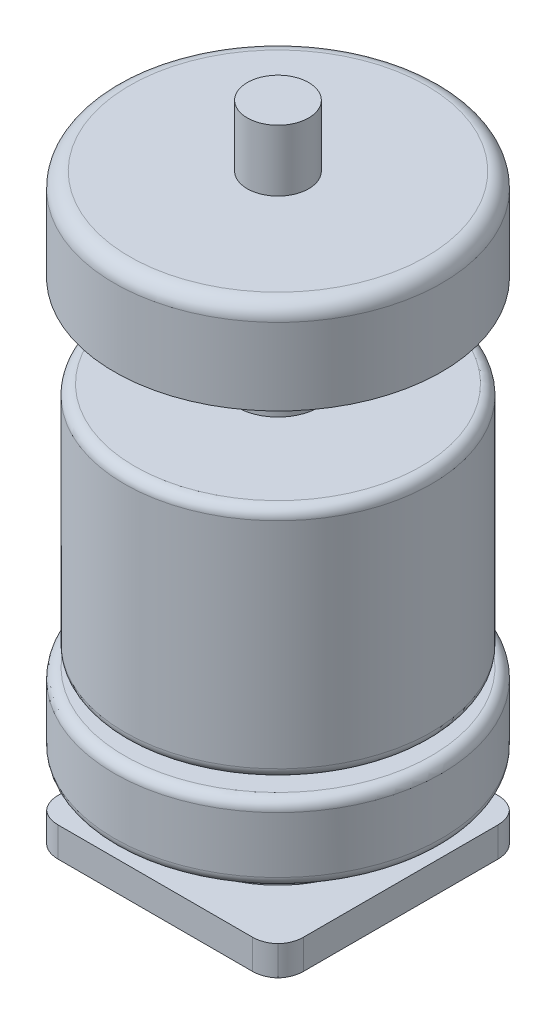
SolidWorks part; units mm, degrees
ref_plane "Ebene vorne" through (0, 0, 0) normal (0, 0, 1) x (1, 0, 0)
ref_plane "Ebene oben" through (0, 0, 0) normal (0, 1, 0) x (1, 0, 0)
ref_plane "Ebene rechts" through (0, 0, 0) normal (1, 0, 0) x (0, 0, -1)
ref_plane "Ebene1" through (0, 0, 10) normal (0, 0, 1) x (1, 0, 0)
ref_plane "Ebene2" through (0, 0, 0) normal (0, 1, 0) x (1, 0, 0)
ref_plane "Ebene3" through (0, 0, 0) normal (1, 0, 0) x (0, 0, -1)
sketch "Skizze1" plane through (0, 0, 0) normal (1, 0, 0) x (0, 0, -1)
  line L0 (-10, 34.65) -> (-10, -34.65) construction
  line L1 (-26, 31.3494) -> (6, 31.3494)
  line L2 (-26, 31.3494) -> (-26, -31.6506)
  line L3 (-26, -31.6506) -> (6, -31.6506)
  line L4 (6, 31.3494) -> (6, -31.6506)
  line L5 (-10, 31.3494) -> (-10, -31.6506)
  point P4 (-10, 31.3494)
  dimension "D1" = 63
  dimension "D2" = 32
revolve "Rotation1" add sketch "Skizze1" angle 360 about L5 region at (0, -0.1506, 18)
sketch "Skizze2" plane through (0, 31.3494, 0) normal (0, 1, 0) x (1, 0, 0)
  circle A0 centre (0, -10) radius 3
  circle A1 centre (0, -10) radius 16
  point P4 (0, 0)
ref_axis "Achse1" through (0, 55, 10) along (0, -1, 0)
sketch "Skizze6" plane through (0, 0, 10) normal (0, 0, 1) x (1, 0, 0)
  line L0 (0, 55) -> (0, -55) construction
  line L1 (-3, 31.3494) -> (-17.0561, 31.3494)
  line L2 (-3, 31.3494) -> (-3, 25.3494)
  line L3 (-3, 25.3494) -> (-17.0561, 25.3494)
  line L4 (-17.0561, 31.3494) -> (-17.0561, 25.3494)
  line L6 (3, 31.3494) -> (-3, 31.3494) construction
  point P8 (0, 0)
  dimension "D1" = 3
  dimension "D2" = 6
revolve "Schnitt-Rotation1" cut sketch "Skizze6" angle 360 about axis through (0, 55, 10) along (0, -1, 0)
sketch "Skizze7" plane through (0, -31.6506, 0) normal (0, -1, 0) x (1, 0, 0)
  line L0 (17.6, 10) -> (-17.6, 10) construction
  line L1 (12, 22) -> (-12, 22)
  line L2 (12, 22) -> (12, -2)
  line L3 (12, -2) -> (-12, -2)
  line L4 (-12, 22) -> (-12, -2)
  line L5 (0, -55) -> (0, 55) construction
  circle A1 centre (0, 10) radius 16.9706
  point P6 (-12, 10)
  point P7 (0, 22)
  point P10 (0, -2)
  point P13 (0, 0)
  circle M5 centre (0, 10) radius 16
  dimension "D1" = 24
  dimension "D2" = 24
extrude "Schnitt-Linear austragen2" cut sketch "Skizze7" against normal blind 2.9 contours L1 M5 | L2 M5 | L3 M5 | L4 M5 region at (0, -31.6506, 23.6185) region at (13.6185, -31.6506, 10) region at (-13.6185, -31.6506, 10) region at (0, -31.6506, -3.6185)
sketch "Skizze8" plane through (0, 0, 10) normal (0, 0, 1) x (1, 0, 0)
  line L1 (-9, -28.7506) -> (-18.6979, -28.7506)
  line L2 (-9, -28.7506) -> (-9, -24.1451)
  line L3 (-9, -24.1451) -> (-18.6979, -24.1451)
  line L4 (-18.6979, -28.7506) -> (-18.6979, -24.1451)
  line L5 (10.583, -31.6506) -> (-10.583, -31.6506) construction
  line L6 (0, 55) -> (0, -55) construction
  dimension "D1" = 2.9
  dimension "D2" = 9
revolve "Schnitt-Rotation2" cut sketch "Skizze8" angle 360 about axis through (0, 55, 10) along (0, -1, 0)
fillet "Verrundung1" radius 2.7 8 edges at (-12, -30.2006, -0.583) (-10.583, -30.2006, -2) (-10.583, -30.2006, 22) (-12, -30.2006, 20.583) (10.583, -30.2006, 22) (12, -30.2006, 20.583) (10.583, -30.2006, -2) (12, -30.2006, -0.583)
sketch "Skizze9" plane through (0, 0, 10) normal (0, 0, 1) x (1, 0, 0)
  line L0 (16, 25.3494) -> (-16, 25.3494) construction
  line L1 (4, 7.3494) -> (17.5123, 7.3494)
  line L2 (4, 7.3494) -> (4, 16.3494)
  line L3 (4, 16.3494) -> (17.5123, 16.3494)
  line L4 (17.5123, 7.3494) -> (17.5123, 16.3494)
  line L5 (0, 55) -> (0, -55) construction
  dimension "D1" = 9
  dimension "D2" = 9
  dimension "D3" = 4
revolve "Schnitt-Rotation3" cut sketch "Skizze9" angle 360 about axis through (0, 55, 10) along (0, -1, 0)
sketch "Skizze11" plane through (0, 0, 10) normal (0, 0, 1) x (1, 0, 0)
  line L0 (9.5079, -31.6506) -> (-9.5079, -31.6506) construction
  line L1 (-15, -16.6506) -> (-17.7938, -16.6506)
  line L2 (-15, -16.6506) -> (-15, 7.8274)
  line L3 (-15, 7.8274) -> (-17.7938, 7.8274)
  line L4 (-17.7938, -16.6506) -> (-17.7938, 7.8274)
  line L5 (-16, 7.3494) -> (-16, -24.1451) construction
  dimension "D1" = 15
  dimension "D2" = 1
revolve "Schnitt-Rotation4" cut sketch "Skizze11" angle 360 about axis through (0, 55, 10) along (0, -1, 0)
sketch "Skizze12" plane through (0, 0, 10) normal (0, 0, 1) x (1, 0, 0)
  line L0 (16, -16.6506) -> (-16, -16.6506) construction
  line L1 (-9, -16.6506) -> (-17.5865, -16.6506)
  line L2 (-9, -16.6506) -> (-9, -15.6506)
  line L3 (-9, -15.6506) -> (-17.5865, -15.6506)
  line L4 (-17.5865, -16.6506) -> (-17.5865, -15.6506)
  line L5 (-15, 7.3494) -> (-15, -15.6506) construction
  dimension "D1" = 0
  dimension "D2" = 1
  dimension "D3" = 6
revolve "Schnitt-Rotation5" cut sketch "Skizze12" angle 360 about axis through (0, 55, 10) along (0, -1, 0)
fillet "Verrundung2" radius 1.5 1 edges at (0, 25.3494, -6)
fillet "Verrundung3" radius 1 2 edges at (0, -24.1451, 26) (0, -16.6506, -6)
fillet "Verrundung4" radius 1 2 edges at (0, 7.3494, 25) (0, -15.6506, 25)
